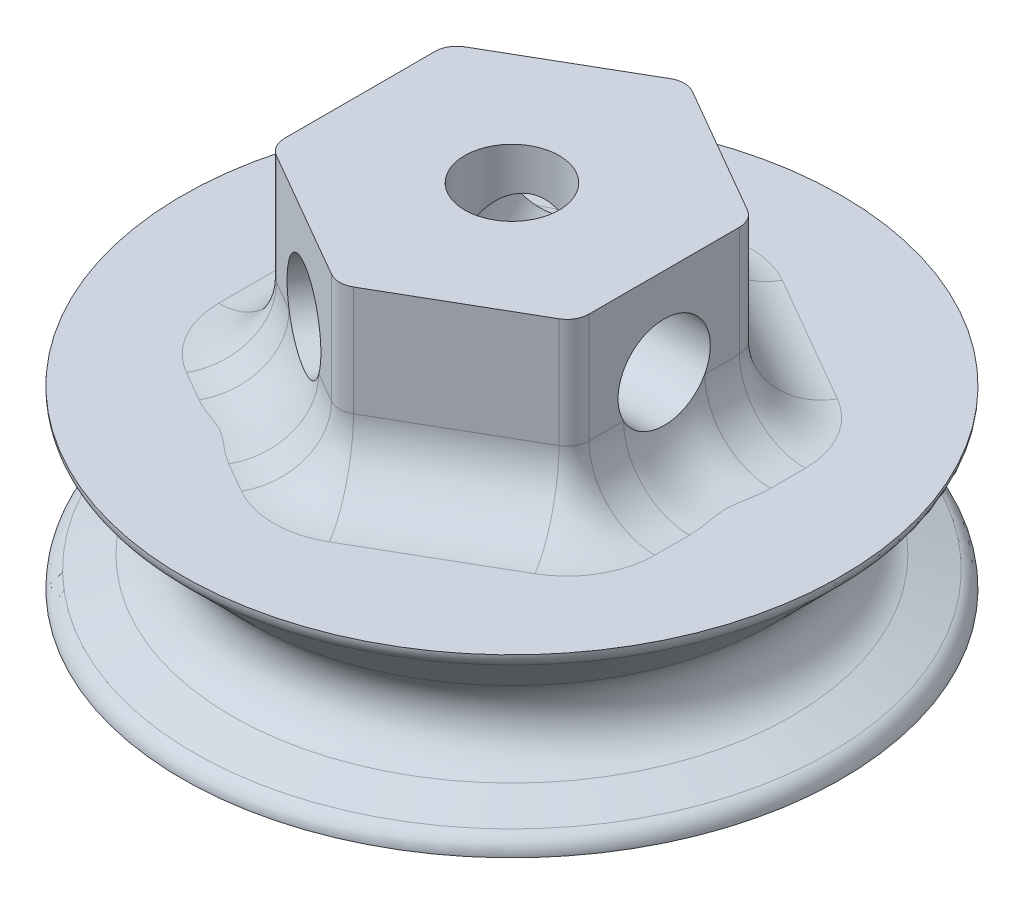
SolidWorks part; units mm, degrees
ref_plane "Front Plane" through (0, 0, 0) normal (0, 0, 1) x (1, 0, 0)
ref_plane "Top Plane" through (0, 0, 0) normal (0, 1, 0) x (1, 0, 0)
ref_plane "Right Plane" through (0, 0, 0) normal (1, 0, 0) x (0, 0, -1)
sketch "Sketch1" plane through (0, 0, 0) normal (0, 0, 1) x (1, 0, 0)
  line L0 (-2.15, 0) -> (-2.15, 8)
  line L1 (-2.15, 8) -> (-15, 8)
  line L2 (-14.7657, 7.4343) -> (-11.9858, 4.6544)
  line L3 (-12.7455, 1.3503) -> (-14.4618, 0.756)
  line L4 (-15, 0) -> (-2.15, 0)
  line L5 (0, 0) -> (0, 15.8767) construction
  arc A0 (-15, 8) -> (-14.7657, 7.4343) centre (-14.2, 8) ccw
  arc A1 (-11.9858, 4.6544) -> (-12.7455, 1.3503) centre (-13.4, 3.2402) cw
  arc A2 (-15, 0) -> (-14.4618, 0.756) centre (-14.2, 0) cw
  dimension "D1" = 8
  dimension "D4" = 2
  dimension "D5" = 0.8
  dimension "D2" = 2.15
  dimension "D3" = 15
  dimension "D6" = 45
  dimension "D7" = 13.4
revolve "Revolve1" add sketch "Sketch1" angle 360 about L5
sketch "Sketch2" plane through (0, 8, 0) normal (0, 1, 0) x (1, 0, 0)
  line L1 (0, 8) -> (-6.9282, 4)
  line L2 (-6.9282, 4) -> (-6.9282, -4)
  line L3 (-6.9282, -4) -> (0, -8)
  line L4 (0, -8) -> (6.9282, -4)
  line L5 (6.9282, -4) -> (6.9282, 4)
  line L6 (6.9282, 4) -> (0, 8)
  circle A0 centre (0, 0) radius 2.15
  circle A1 centre (0, 0) radius 6.9282 construction
  circle A2 centre (0, 0) radius 2.15 construction
  dimension "D1" = 8
extrude "Boss-Extrude1" add sketch "Sketch2" along normal blind 8
sketch "Sketch3" plane through (-3.4641, 0, 6) normal (-0.5, 0, 0.866) x (0.866, 0, 0.5)
  line L0 (-4, 16) -> (4, 8) construction
  circle A0 centre (0, 12) radius 2.1
  dimension "D1" = 4.2
extrude "Cut-Extrude1" cut sketch "Sketch3" against normal up to next
ref_axis "Axis1" through (0, 16, 0) along (0, -1, 0)
pattern_circular "CirPattern1" count 3 over 360 about axis through (0, 16, 0) along (0, -1, 0) of "Cut-Extrude1"
fillet "Fillet1" radius 1 6 edges at (-6.9282, 12, -4) (0, 12, -8) (6.9282, 12, -4) (6.9282, 12, 4) (0, 12, 8) (-6.9282, 12, 4)
fillet "Fillet2" radius 3 12 edges at (-6.7942, 8, 3.9226) (-6.9282, 8, 0) (-6.7942, 8, -3.9226) (-3.4641, 8, -6) (0, 8, -7.8453) (3.4641, 8, -6) (6.7942, 8, -3.9226) (6.9282, 8, 0) (6.7942, 8, 3.9226) (3.4641, 8, 6) (0, 8, 7.8453) (-3.4641, 8, 6)
